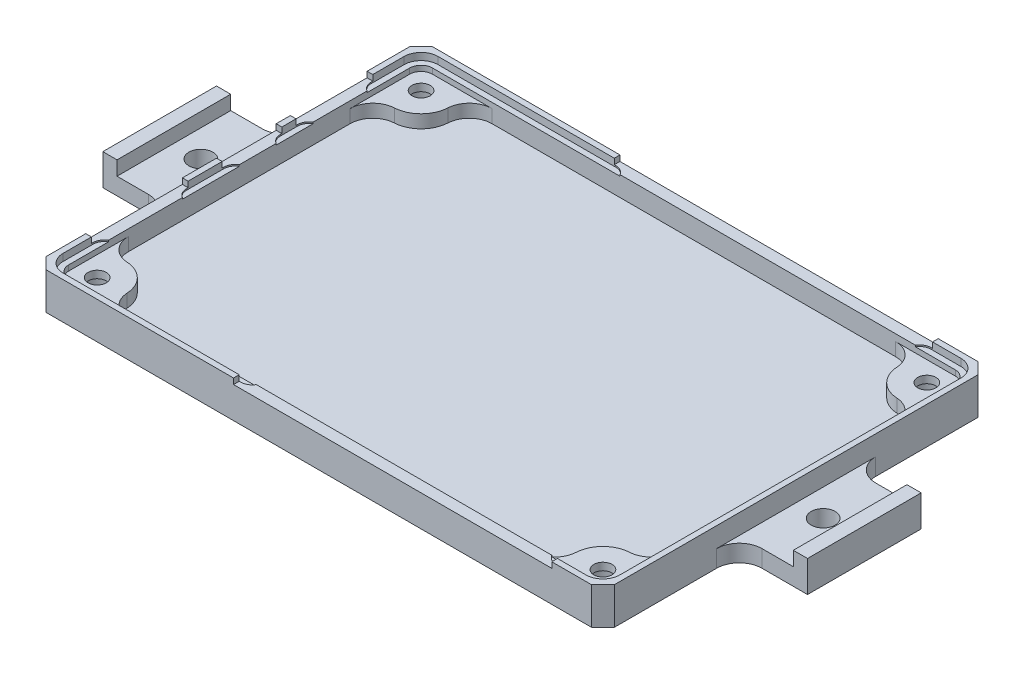
SolidWorks part; units mm, degrees
ref_plane "Front Plane" through (0, 0, 0) normal (0, 0, 1) x (1, 0, 0)
ref_plane "Top Plane" through (0, 0, 0) normal (0, 1, 0) x (1, 0, 0)
ref_plane "Right Plane" through (0, 0, 0) normal (1, 0, 0) x (0, 0, -1)
sketch "Sketch1" plane through (0, 0, 0) normal (0, 1, 0) x (1, 0, 0)
  line L0 (-105.3563, -14.3722) -> (-103.3563, -12.3722)
  line L1 (-103.3563, -12.3722) -> (-7.3563, -12.3722)
  line L2 (-105.3563, -14.3722) -> (-105.3563, -78.3722)
  line L3 (-103.3563, -80.3722) -> (-7.3563, -80.3722)
  line L4 (-5.3563, -14.3722) -> (-5.3563, -78.3722)
  line L5 (-105.3563, -78.3722) -> (-103.3563, -80.3722)
  line L6 (-7.3563, -80.3722) -> (-5.3563, -78.3722)
  line L7 (-7.3563, -12.3722) -> (-5.3563, -14.3722)
  point P0 (-105.3563, -12.3722)
  point P1 (-5.3563, -80.3722)
  point P2 (-105.3563, -80.3722)
  point P3 (-5.3563, -12.3722)
  dimension "D1" = 100
  dimension "D2" = 68
extrude "Boss-Extrude1" add sketch "Sketch1" along normal blind 5.5
sketch "Sketch2" plane through (0, 5.5, 0) normal (0, 1, 0) x (1, 0, 0)
  line L0 (-105.3563, -14.3722) -> (-105.3563, -78.3722) construction
  line L1 (-101.3563, -14.3722) -> (-9.3563, -14.3722)
  line L2 (-103.3563, -16.3722) -> (-103.3563, -76.3722)
  line L3 (-101.3563, -78.3722) -> (-9.3563, -78.3722)
  line L4 (-7.3563, -16.3722) -> (-7.3563, -76.3722)
  line L5 (-7.3563, -12.3722) -> (-103.3563, -12.3722) construction
  line L6 (-103.3563, -80.3722) -> (-7.3563, -80.3722) construction
  line L7 (-5.3563, -78.3722) -> (-5.3563, -14.3722) construction
  arc A0 (-7.3563, -16.3722) -> (-9.3563, -14.3722) centre (-9.3563, -16.3722) ccw
  arc A1 (-103.3563, -16.3722) -> (-101.3563, -14.3722) centre (-101.3563, -16.3722) cw
  arc A2 (-101.3563, -78.3722) -> (-103.3563, -76.3722) centre (-101.3563, -76.3722) cw
  arc A3 (-9.3563, -78.3722) -> (-7.3563, -76.3722) centre (-9.3563, -76.3722) ccw
  point P0 (-103.3563, -14.3722)
  point P1 (-7.3563, -78.3722)
  point P2 (-103.3563, -78.3722)
  point P3 (-7.3563, -14.3722)
  dimension "D5" = 2
  dimension "D6" = 2
  dimension "D7" = 2
  dimension "D8" = 2
  dimension "D1" = 2
  dimension "D2" = 2
  dimension "D3" = 2
  dimension "D4" = 2
extrude "pcb basin" cut sketch "Sketch2" against normal offset from surface (3.5 mm away) 2 up to face at (-55.3563, 0, 46.3722)
sketch "Sketch3" plane through (0, 2, 0) normal (0, 1, 0) x (1, 0, 0)
  line L0 (-103.3563, -80.3722) -> (-7.3563, -80.3722) construction
  line L1 (-55.3563, -12.3722) -> (-55.3563, -80.3722) construction
  line L2 (-103.3563, -69.8722) -> (-99.8563, -69.8722)
  line L4 (-105.3563, -14.3722) -> (-105.3563, -78.3722) construction
  line L5 (-101.3563, -78.3722) -> (-9.3563, -78.3722) construction
  line L6 (-94.8563, -74.8722) -> (-94.8563, -78.3722)
  line L7 (-7.3563, -12.3722) -> (-103.3563, -12.3722) construction
  line L8 (-105.3563, -46.3722) -> (-5.3563, -46.3722) construction
  line L9 (-105.3563, -14.3722) -> (-105.3563, -78.3722) construction
  line L10 (-5.3563, -78.3722) -> (-5.3563, -14.3722) construction
  line L11 (-7.3563, -69.8722) -> (-7.3563, -76.3722)
  line L12 (-101.3563, -78.3722) -> (-94.8563, -78.3722)
  line L13 (-103.3563, -69.8722) -> (-103.3563, -76.3722)
  line L14 (-9.3563, -78.3722) -> (-15.8563, -78.3722)
  line L15 (-15.8563, -74.8722) -> (-15.8563, -78.3722)
  line L16 (-7.3563, -69.8722) -> (-10.8563, -69.8722)
  line L17 (-7.3563, -22.8722) -> (-10.8563, -22.8722)
  line L18 (-15.8563, -17.8722) -> (-15.8563, -14.3722)
  line L19 (-9.3563, -14.3722) -> (-15.8563, -14.3722)
  line L20 (-103.3563, -22.8722) -> (-103.3563, -16.3722)
  line L21 (-101.3563, -14.3722) -> (-94.8563, -14.3722)
  line L22 (-7.3563, -22.8722) -> (-7.3563, -16.3722)
  line L23 (-94.8563, -17.8722) -> (-94.8563, -14.3722)
  line L24 (-103.3563, -16.3722) -> (-103.3563, -76.3722) construction
  line L25 (-103.3563, -22.8722) -> (-99.8563, -22.8722)
  line L27 (-101.3563, -78.3722) -> (-9.3563, -78.3722) construction
  arc A0 (-103.3563, -76.3722) -> (-101.3563, -78.3722) centre (-101.3563, -76.3722) ccw construction
  arc A1 (-103.3563, -76.3722) -> (-101.3563, -78.3722) centre (-101.3563, -76.3722) ccw
  arc A2 (-10.8563, -69.8722) -> (-15.8563, -74.8722) centre (-10.8563, -74.8722) ccw
  arc A3 (-7.3563, -76.3722) -> (-9.3563, -78.3722) centre (-9.3563, -76.3722) cw
  arc A4 (-99.8563, -69.8722) -> (-94.8563, -74.8722) centre (-99.8563, -74.8722) cw
  arc A5 (-99.8563, -22.8722) -> (-94.8563, -17.8722) centre (-99.8563, -17.8722) ccw
  arc A6 (-7.3563, -16.3722) -> (-9.3563, -14.3722) centre (-9.3563, -16.3722) ccw
  arc A7 (-10.8563, -22.8722) -> (-15.8563, -17.8722) centre (-10.8563, -17.8722) cw
  arc A8 (-103.3563, -16.3722) -> (-101.3563, -14.3722) centre (-101.3563, -16.3722) cw
  dimension "D8" = 5
  dimension "D6" = 10.5
  dimension "D7" = 10.5
extrude "pcb posts" add sketch "Sketch3" along normal offset from surface (2.3 mm away) 1.2 up to face at (-55.3563, 5.5, 46.3722)
sketch "Sketch4" plane through (0, 0, 0) normal (0, -1, 0) x (1, 0, 0)
  line L0 (-7.3563, 12.3722) -> (-103.3563, 12.3722) construction
  line L1 (-105.3563, 14.3722) -> (-105.3563, 78.3722) construction
  circle A0 centre (-99.8563, 17.8722) radius 1.6
  circle A1 centre (-10.8563, 17.8722) radius 1.6
  circle A2 centre (-10.8563, 74.8722) radius 1.6
  circle A3 centre (-99.8563, 74.8722) radius 1.6
  dimension "D1" = 3.2
  dimension "D4" = 5.5
  dimension "D5" = 5.5
  dimension "D2" = 2
  dimension "D3" = 2
extrude "screw holes" cut sketch "Sketch4" against normal through all
sketch "Sketch6" plane through (0, 0, 0) normal (0, -1, 0) x (1, 0, 0)
  line L0 (-7.3563, 12.3722) -> (-103.3563, 12.3722) construction
  line L1 (-105.3563, 14.3722) -> (-105.3563, 78.3722) construction
  circle A0 centre (-99.8563, 17.8722) radius 3
  circle A1 centre (-10.8563, 17.8722) radius 3
  circle A2 centre (-10.8563, 74.8722) radius 3
  circle A3 centre (-99.8563, 74.8722) radius 3
  dimension "D1" = 6
  dimension "D4" = 5.5
  dimension "D5" = 5.5
  dimension "D2" = 2
  dimension "D3" = 2
extrude "screw chamfer" cut sketch "Sketch6" against normal blind 3
sketch "Sketch11" plane through (0, 5.5, 0) normal (0, 1, 0) x (1, 0, 0)
  line L8 (-7.3563, -12.3722) -> (-103.3563, -12.3722)
  line L9 (-103.3563, -12.3722) -> (-105.3563, -14.3722)
  line L10 (-105.3563, -14.3722) -> (-105.3563, -78.3722)
  line L11 (-105.3563, -78.3722) -> (-103.3563, -80.3722)
  line L12 (-103.3563, -80.3722) -> (-7.3563, -80.3722)
  line L13 (-7.3563, -80.3722) -> (-5.3563, -78.3722)
  line L14 (-5.3563, -78.3722) -> (-5.3563, -14.3722)
  line L15 (-5.3563, -14.3722) -> (-7.3563, -12.3722)
  line L16 (-7.3563, -12.3722) -> (-103.3563, -12.3722)
  line L17 (-103.3563, -12.3722) -> (-105.3563, -14.3722)
  line L18 (-105.3563, -14.3722) -> (-105.3563, -78.3722)
  line L19 (-105.3563, -78.3722) -> (-103.3563, -80.3722)
  line L20 (-103.3563, -80.3722) -> (-7.3563, -80.3722)
  line L21 (-7.3563, -80.3722) -> (-5.3563, -78.3722)
  line L22 (-5.3563, -78.3722) -> (-5.3563, -14.3722)
  line L23 (-5.3563, -14.3722) -> (-7.3563, -12.3722)
  line L128 (-7.7705, -13.3722) -> (-102.9421, -13.3722)
  line L129 (-102.9421, -13.3722) -> (-104.3563, -14.7864)
  line L130 (-104.3563, -14.7864) -> (-104.3563, -77.958)
  line L131 (-104.3563, -77.958) -> (-102.9421, -79.3722)
  line L132 (-102.9421, -79.3722) -> (-7.7705, -79.3722)
  line L133 (-7.7705, -79.3722) -> (-6.3563, -77.958)
  line L134 (-6.3563, -77.958) -> (-6.3563, -14.7864)
  line L135 (-6.3563, -14.7864) -> (-7.7705, -13.3722)
  line L136 (-9.3563, -13.3722) -> (-101.3563, -13.3722)
  line L138 (-104.3563, -16.3722) -> (-104.3563, -76.3722)
  line L140 (-101.3563, -79.3722) -> (-9.3563, -79.3722)
  line L142 (-6.3563, -76.3722) -> (-6.3563, -16.3722)
  arc A0 (-101.3563, -79.3722) -> (-104.3563, -76.3722) centre (-101.3563, -76.3722) cw
  arc A1 (-104.3563, -16.3722) -> (-101.3563, -13.3722) centre (-101.3563, -16.3722) cw
  arc A2 (-9.3563, -79.3722) -> (-6.3563, -76.3722) centre (-9.3563, -76.3722) ccw
  arc A3 (-6.3563, -16.3722) -> (-9.3563, -13.3722) centre (-9.3563, -16.3722) ccw
  dimension "D3" = 3
  dimension "D4" = 3
  dimension "D5" = 3
  dimension "D6" = 3
  dimension "D1" = 0
  dimension "D2" = 1
extrude "lip" add sketch "Sketch11" along normal blind 1
fillet "basin fillet" radius 4 8 edges at (-94.8563, 3.15, 78.3722) (-103.3563, 3.15, 69.8722) (-15.8563, 3.15, 78.3722) (-7.3563, 3.15, 69.8722) (-15.8563, 3.15, 14.3722) (-7.3563, 3.15, 22.8722) (-94.8563, 3.15, 14.3722) (-103.3563, 3.15, 22.8722)
sketch "Sketch12" plane through (-105.3563, 0, 0) normal (-1, 0, 0) x (0, 0, 1)
  line L1 (22.3722, 5.5) -> (34.8722, 5.5) construction
  line L2 (35.3722, 5.5) -> (21.8722, 5.5)
  line L3 (35.3722, 5.5) -> (35.3722, 6.75)
  line L4 (35.3722, 6.75) -> (21.8722, 6.75)
  line L8 (38.3722, 5.5) -> (47.8722, 5.5) construction
  line L9 (37.8722, 5.5) -> (48.3722, 5.5)
  line L10 (37.8722, 5.5) -> (37.8722, 6.75)
  line L11 (37.8722, 6.75) -> (48.3722, 6.75)
  line L12 (48.3722, 5.5) -> (48.3722, 6.75)
  line L13 (78.3722, 6.75) -> (71.3722, 6.75) construction
  line L14 (38.3722, 16.5) -> (38.3722, 5.5) construction
  line L15 (47.8722, 16.5) -> (47.8722, 5.5) construction
  line L16 (21.8722, 5.5) -> (21.8722, 6.75)
  line L17 (22.3722, 16.5) -> (22.3722, 5.5) construction
  line L18 (34.8722, 16.5) -> (34.8722, 5.5) construction
  line L19 (54.8722, 18.5) -> (54.8722, 5.5) construction
  line L20 (71.3722, 6.75) -> (54.3722, 6.75)
  line L21 (71.3722, 6.75) -> (71.3722, 5.5)
  line L22 (71.3722, 5.5) -> (54.3722, 5.5)
  line L23 (54.3722, 6.75) -> (54.3722, 5.5)
  line L24 (70.8722, 18.5) -> (70.8722, 5.5) construction
  dimension "D1" = 0.5
  dimension "D2" = 0.5
  dimension "D3" = 0.5
  dimension "D4" = 0.5
  dimension "D5" = 0.5
  dimension "D6" = 0.5
extrude "interface connector cutout" cut sketch "Sketch12" against normal blind 10
sketch "Sketch13" plane through (0, 0, 12.3722) normal (0, 0, -1) x (-1, 0, 0)
  line L0 (7.3563, 6.5) -> (103.3563, 6.5) construction
  line L1 (14.3563, 6.5) -> (70.3563, 6.5)
  line L2 (14.3563, 6.5) -> (14.3563, 5.5)
  line L3 (14.3563, 5.5) -> (70.3563, 5.5)
  line L4 (70.3563, 6.5) -> (70.3563, 5.5)
  line L5 (63.8563, 5.5) -> (69.8563, 5.5) construction
  line L6 (69.8563, 10.25) -> (69.8563, 5.5) construction
  line L7 (14.8563, 10.25) -> (14.8563, 5.5) construction
  dimension "D1" = 0.5
  dimension "D2" = 0.5
extrude "pop connector cutout" cut sketch "Sketch13" against normal through all
sketch "Sketch14" plane through (0, 5.5, 0) normal (0, 1, 0) x (1, 0, 0)
  line L0 (-103.3563, -37.8722) -> (-103.3563, -39.8722)
  line L1 (-103.3563, -26.8583) -> (-103.3563, -16.3722) construction
  line L3 (-103.3563, -26.8583) -> (-103.3563, -65.8861) construction
  line L5 (-103.3563, -35.3722) -> (-103.3563, -37.8722)
  line L9 (-9.3563, -14.3722) -> (-101.3563, -14.3722)
  line L10 (-7.3563, -76.3722) -> (-7.3563, -16.3722)
  line L11 (-101.3563, -78.3722) -> (-9.3563, -78.3722)
  line L12 (-103.3563, -16.3722) -> (-103.3563, -76.3722)
  line L13 (-9.3563, -14.3722) -> (-14.3563, -14.3722)
  line L14 (-7.3563, -76.3722) -> (-7.3563, -16.3722)
  line L15 (-101.3563, -78.3722) -> (-70.3563, -78.3722)
  line L16 (-103.3563, -16.3722) -> (-103.3563, -21.8722)
  line L21 (-103.3563, -48.3722) -> (-103.3563, -54.3722)
  line L22 (-103.3563, -71.3722) -> (-103.3563, -76.3722)
  line L23 (-14.3563, -78.3722) -> (-9.3563, -78.3722)
  line L24 (-101.3563, -79.3722) -> (-70.3563, -79.3722)
  line L25 (-70.3563, -79.3722) -> (-70.3563, -80.3722)
  line L26 (-70.3563, -80.3722) -> (-14.3563, -80.3722)
  line L27 (-14.3563, -80.3722) -> (-14.3563, -79.3722)
  line L28 (-14.3563, -79.3722) -> (-9.3563, -79.3722)
  line L29 (-6.3563, -76.3722) -> (-6.3563, -16.3722)
  line L30 (-9.3563, -13.3722) -> (-14.3563, -13.3722)
  line L31 (-14.3563, -13.3722) -> (-14.3563, -12.3722)
  line L32 (-14.3563, -12.3722) -> (-70.3563, -12.3722)
  line L33 (-70.3563, -12.3722) -> (-70.3563, -13.3722)
  line L34 (-70.3563, -13.3722) -> (-101.3563, -13.3722)
  line L35 (-104.3563, -16.3722) -> (-104.3563, -21.8722)
  line L36 (-104.3563, -21.8722) -> (-105.3563, -21.8722)
  line L37 (-105.3563, -21.8722) -> (-105.3563, -35.3722)
  line L38 (-105.3563, -35.3722) -> (-104.3563, -35.3722)
  line L39 (-104.3563, -35.3722) -> (-104.3563, -37.8722)
  line L40 (-104.3563, -37.8722) -> (-105.3563, -37.8722)
  line L41 (-105.3563, -37.8722) -> (-105.3563, -48.3722)
  line L42 (-105.3563, -48.3722) -> (-104.3563, -48.3722)
  line L43 (-104.3563, -48.3722) -> (-104.3563, -54.3722)
  line L44 (-104.3563, -54.3722) -> (-105.3563, -54.3722)
  line L45 (-105.3563, -54.3722) -> (-105.3563, -71.3722)
  line L46 (-105.3563, -71.3722) -> (-104.3563, -71.3722)
  line L47 (-104.3563, -71.3722) -> (-104.3563, -76.3722)
  line L48 (-101.3563, -79.3722) -> (-70.3563, -79.3722)
  line L49 (-70.3563, -14.3722) -> (-101.3563, -14.3722)
  line L51 (-103.3563, -16.3722) -> (-103.3563, -76.3722) construction
  line L52 (-14.3563, -79.3722) -> (-9.3563, -79.3722)
  line L53 (-6.3563, -76.3722) -> (-6.3563, -16.3722)
  line L54 (-9.3563, -13.3722) -> (-14.3563, -13.3722)
  line L56 (-104.3563, -21.8722) -> (-104.3563, -23.8722)
  line L57 (-104.3563, -23.8722) -> (-103.3563, -23.8722)
  line L58 (-70.3563, -13.3722) -> (-101.3563, -13.3722)
  line L59 (-104.3563, -16.3722) -> (-104.3563, -21.8722)
  line L60 (-103.3563, -21.8722) -> (-103.3563, -23.8722)
  line L62 (-104.3563, -35.3722) -> (-104.3563, -33.3722)
  line L63 (-104.3563, -35.3722) -> (-104.3563, -37.8722)
  line L64 (-104.3563, -33.3722) -> (-103.3563, -33.3722)
  line L65 (-103.3563, -35.3722) -> (-103.3563, -33.3722)
  line L67 (-104.3563, -48.3722) -> (-104.3563, -54.3722)
  line L68 (-104.3563, -37.8722) -> (-104.3563, -39.8722)
  line L69 (-104.3563, -39.8722) -> (-103.3563, -39.8722)
  line L71 (-104.3563, -71.3722) -> (-104.3563, -76.3722)
  line L73 (-104.3563, -48.3722) -> (-104.3563, -46.3722)
  line L74 (-104.3563, -46.3722) -> (-103.3563, -46.3722)
  line L75 (-103.3563, -48.3722) -> (-103.3563, -46.3722)
  line L77 (-103.3563, -71.3722) -> (-103.3563, -69.3722)
  line L78 (-103.3563, -69.3722) -> (-104.3563, -69.3722)
  line L79 (-104.3563, -71.3722) -> (-104.3563, -69.3722)
  line L81 (-104.3563, -54.3722) -> (-104.3563, -56.3722)
  line L82 (-104.3563, -56.3722) -> (-103.3563, -56.3722)
  line L83 (-103.3563, -54.3722) -> (-103.3563, -56.3722)
  line L84 (-9.3563, -78.3722) -> (-19.8424, -78.3722) construction
  line L85 (-70.3563, -78.3722) -> (-68.3563, -78.3722)
  line L87 (-70.3563, -79.3722) -> (-68.3563, -79.3722)
  line L88 (-68.3563, -78.3722) -> (-68.3563, -79.3722)
  line L89 (-14.3563, -79.3722) -> (-16.3563, -79.3722)
  line L91 (-14.3563, -78.3722) -> (-16.3563, -78.3722)
  line L92 (-16.3563, -79.3722) -> (-16.3563, -78.3722)
  line L93 (-19.8424, -14.3722) -> (-9.3563, -14.3722) construction
  line L94 (-14.3563, -13.3722) -> (-16.3563, -13.3722)
  line L96 (-14.3563, -14.3722) -> (-16.3563, -14.3722)
  line L97 (-16.3563, -13.3722) -> (-16.3563, -14.3722)
  line L98 (-19.8424, -14.3722) -> (-90.8702, -14.3722) construction
  line L99 (-70.3563, -13.3722) -> (-68.3563, -13.3722)
  line L101 (-70.3563, -14.3722) -> (-68.3563, -14.3722)
  line L102 (-68.3563, -13.3722) -> (-68.3563, -14.3722)
  arc A4 (-9.3563, -79.3722) -> (-6.3563, -76.3722) centre (-9.3563, -76.3722) ccw
  arc A5 (-6.3563, -16.3722) -> (-9.3563, -13.3722) centre (-9.3563, -16.3722) ccw
  arc A6 (-101.3563, -13.3722) -> (-104.3563, -16.3722) centre (-101.3563, -16.3722) ccw
  arc A7 (-104.3563, -76.3722) -> (-101.3563, -79.3722) centre (-101.3563, -76.3722) ccw
  arc A8 (-9.3563, -79.3722) -> (-6.3563, -76.3722) centre (-9.3563, -76.3722) ccw
  arc A9 (-6.3563, -16.3722) -> (-9.3563, -13.3722) centre (-9.3563, -16.3722) ccw
  arc A10 (-101.3563, -13.3722) -> (-104.3563, -16.3722) centre (-101.3563, -16.3722) ccw
  arc A11 (-104.3563, -76.3722) -> (-101.3563, -79.3722) centre (-101.3563, -76.3722) ccw
  arc A14 (-101.3563, -14.3722) -> (-103.3563, -16.3722) centre (-101.3563, -16.3722) ccw
  arc A15 (-7.3563, -16.3722) -> (-9.3563, -14.3722) centre (-9.3563, -16.3722) ccw
  arc A16 (-9.3563, -78.3722) -> (-7.3563, -76.3722) centre (-9.3563, -76.3722) ccw
  arc A17 (-103.3563, -76.3722) -> (-101.3563, -78.3722) centre (-101.3563, -76.3722) ccw
  arc A18 (-101.3563, -14.3722) -> (-103.3563, -16.3722) centre (-101.3563, -16.3722) ccw
  arc A19 (-7.3563, -16.3722) -> (-9.3563, -14.3722) centre (-9.3563, -16.3722) ccw
  arc A20 (-9.3563, -78.3722) -> (-7.3563, -76.3722) centre (-9.3563, -76.3722) ccw
  arc A21 (-103.3563, -76.3722) -> (-101.3563, -78.3722) centre (-101.3563, -76.3722) ccw
  dimension "D3" = 2
  dimension "D4" = 2
  dimension "D5" = 2
  dimension "D6" = 2
  dimension "D7" = 2
  dimension "D8" = 2
  dimension "D9" = 2
  dimension "D10" = 2
  dimension "D11" = 2
  dimension "D1" = 0
  dimension "D2" = 0
extrude "Cut-Extrude3" cut sketch "Sketch14" against normal blind 0.25
fillet "Fillet7" radius 2 10 edges at (-68.3563, 5.375, 79.3722) (-16.3563, 5.375, 79.3722) (-16.3563, 5.375, 13.3722) (-104.3563, 5.375, 23.8722) (-68.3563, 5.375, 13.3722) (-104.3563, 5.375, 69.3722) (-104.3563, 5.375, 46.3722) (-104.3563, 5.375, 56.3722) (-104.3563, 5.375, 39.8722) (-104.3563, 5.375, 33.3722)
sketch "Sketch15" plane through (0, 0, 0) normal (0, -1, 0) x (1, 0, 0)
  line L0 (-105.3563, 14.3722) -> (-105.3563, 78.3722) construction
  line L1 (-105.3563, 56.3722) -> (-117.3563, 56.3722)
  line L2 (-105.3563, 56.3722) -> (-105.3563, 36.3722)
  line L3 (-105.3563, 36.3722) -> (-117.3563, 36.3722)
  line L4 (-117.3563, 56.3722) -> (-117.3563, 36.3722)
  line L5 (6.6437, 56.3722) -> (6.6437, 36.3722)
  line L6 (-103.3563, 80.3722) -> (-7.3563, 80.3722) construction
  line L7 (-5.3563, 36.3722) -> (6.6437, 36.3722)
  line L8 (-5.3563, 56.3722) -> (-5.3563, 36.3722)
  line L9 (-55.3563, 80.3722) -> (-55.3563, 12.3722) construction
  line L10 (-7.3563, 12.3722) -> (-103.3563, 12.3722) construction
  line L11 (-5.3563, 56.3722) -> (6.6437, 56.3722)
  dimension "D1" = 12
  dimension "D2" = 20
  dimension "D3" = 24
extrude "mounting pegs" add sketch "Sketch15" against normal blind 3
fillet "mounting pegs fillet" radius 4 4 edges
sketch "mounting peg lips" plane through (0, 3, 0) normal (0, 1, 0) x (1, 0, 0)
  line L0 (-109.3563, -56.3722) -> (-117.3563, -56.3722) construction
  line L1 (-117.3563, -36.3722) -> (-114.8563, -36.3722)
  line L2 (-117.3563, -36.3722) -> (-117.3563, -56.3722)
  line L3 (-117.3563, -56.3722) -> (-114.8563, -56.3722)
  line L4 (-114.8563, -36.3722) -> (-114.8563, -56.3722)
  line L6 (6.6437, -56.3722) -> (-1.3563, -56.3722) construction
  line L7 (6.6437, -36.3722) -> (4.1437, -36.3722)
  line L8 (6.6437, -36.3722) -> (6.6437, -56.3722)
  line L9 (6.6437, -56.3722) -> (4.1437, -56.3722)
  line L10 (4.1437, -36.3722) -> (4.1437, -56.3722)
  dimension "D1" = 2.5
  dimension "D2" = 2.5
extrude "Boss-Extrude3" add sketch "mounting peg lips" along normal blind 2.5
sketch "Sketch17" plane through (0, 3, 0) normal (0, 1, 0) x (1, 0, 0)
  line L0 (-114.8563, -36.3722) -> (-109.3563, -36.3722) construction
  line L1 (-117.3563, -36.3722) -> (-117.3563, -56.3722) construction
  line L2 (-1.3563, -36.3722) -> (4.1437, -36.3722) construction
  line L3 (6.6437, -56.3722) -> (6.6437, -36.3722) construction
  circle A0 centre (-110.1063, -46.3722) radius 2.1
  circle A1 centre (-0.6063, -46.3722) radius 2.1
  point P8 (1.3937, -36.3722)
  dimension "D5" = 4.2
  dimension "D6" = 4.2
  dimension "D1" = 10
  dimension "D2" = 7.25
  dimension "D3" = 10
  dimension "D4" = 7.25
extrude "Cut-Extrude4" cut sketch "Sketch17" against normal up to surface (3 mm away) up to face at (-99.8563, 0, 71.8722)
